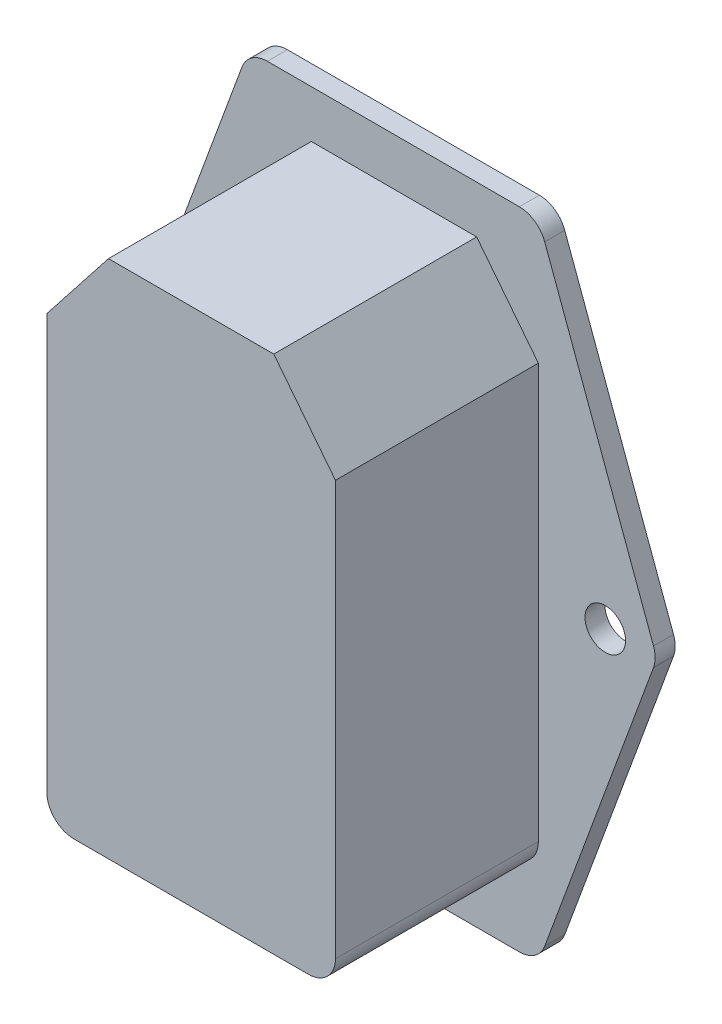
SolidWorks part; units mm, degrees
ref_plane "Front Plane" through (0, 0, 0) normal (0, 0, 1) x (1, 0, 0)
ref_plane "Top Plane" through (0, 0, 0) normal (0, 1, 0) x (1, 0, 0)
ref_plane "Right Plane" through (0, 0, 0) normal (1, 0, 0) x (0, 0, -1)
sketch "Sketch1" plane through (0, 0, 0) normal (0, 0, 1) x (1, 0, 0)
  line L0 (2.54, 0) -> (24.5618, 0)
  line L1 (27.1018, 2.54) -> (27.1018, 41.4401)
  line L2 (27.1018, 41.4401) -> (21.3106, 48.8095)
  line L3 (21.3106, 48.8095) -> (5.7912, 48.8095)
  line L4 (0, 2.54) -> (0, 41.4401)
  line L5 (0, 41.4401) -> (5.7912, 48.8095)
  arc A0 (2.54, 0) -> (0, 2.54) centre (2.54, 2.54) cw
  arc A1 (24.5618, 0) -> (27.1018, 2.54) centre (24.5618, 2.54) ccw
  point P10 (0, 0)
  point P13 (27.1018, 0)
  dimension "D5" = 2.54
  dimension "D7" = 2.54
  dimension "D1" = 27.1018
  dimension "D2" = 41.4401
  dimension "D3" = 9.3726
  dimension "D4" = 15.5194
  dimension "D6" = 9.3726
extrude "Boss-Extrude1" add sketch "Sketch1" along normal blind 19.05
sketch "Sketch2" plane through (0, 0, 0) normal (0, 0, 1) x (1, 0, 0)
  line L0 (1.6576, 53.2672) -> (25.3172, 53.2672)
  line L2 (27.1018, 2.54) -> (27.1018, 41.4401) construction
  line L3 (0, 41.4401) -> (0, 2.54) construction
  line L4 (21.3106, 48.8095) -> (5.7912, 48.8095) construction
  line L7 (27.701, 51.6043) -> (37.9145, 23.8468)
  line L8 (37.9145, 22.0925) -> (27.701, -5.665)
  line L9 (25.3172, -7.3279) -> (1.6576, -7.3279)
  line L10 (-0.7262, -5.665) -> (-10.9397, 22.0925)
  line L11 (-10.9397, 23.8468) -> (-0.7262, 51.6043)
  line L12 (2.54, 0) -> (24.5618, 0) construction
  arc A0 (1.6576, -7.3279) -> (-0.7262, -5.665) centre (1.6576, -4.7879) cw
  arc A1 (-10.9397, 22.0925) -> (-10.9397, 23.8468) centre (-8.556, 22.9696) cw
  arc A2 (27.701, -5.665) -> (25.3172, -7.3279) centre (25.3172, -4.7879) cw
  arc A3 (37.9145, 22.0925) -> (37.9145, 23.8468) centre (35.5308, 22.9696) ccw
  arc A4 (27.701, 51.6043) -> (25.3172, 53.2672) centre (25.3172, 50.7272) ccw
  arc A5 (-0.7262, 51.6043) -> (1.6576, 53.2672) centre (1.6576, 50.7272) cw
  point P16 (27.1018, 21.9901)
  point P21 (-11.2625, 22.9696)
  point P26 (38.2373, 22.9696)
  point P29 (27.0891, 53.2672)
  point P32 (-0.1143, 53.2672)
  dimension "D7" = 2.54
  dimension "D1" = 27.2034
  dimension "D2" = 4.4577
  dimension "D3" = 5.7785
  dimension "D4" = 7.3279
  dimension "D5" = 11.1355
  dimension "D6" = 11.2625
sketch "Sketch5" plane through (0, 0, 0) normal (0, 0, 1) x (1, 0, 0)
extrude "Boss-Extrude2" add sketch "Sketch2" against normal blind 1.8796
sketch "Sketch6" plane through (0, 0, 0) normal (0, 0, 1) x (1, 0, 0)
  line L0 (1.6576, -7.3279) -> (25.3172, -7.3279) construction
  circle A0 centre (33.3845, 22.9696) radius 1.905
  circle A1 centre (-6.4097, 22.9696) radius 1.905
  arc A3 (37.9145, 22.0925) -> (37.9145, 23.8468) centre (35.5308, 22.9696) ccw construction
  arc A4 (-10.9397, 23.8468) -> (-10.9397, 22.0925) centre (-8.556, 22.9696) ccw construction
  point P9 (38.0708, 22.9696)
  point P13 (-11.096, 22.9696)
  dimension "D1" = 3.81
  dimension "D2" = 4.6863
  dimension "D3" = 4.6863
  dimension "D4" = 30.2975
  dimension "D5" = 30.2975
extrude "Cut-Extrude1" cut sketch "Sketch6" against normal blind 20.4216 and the other way blind 22.606
